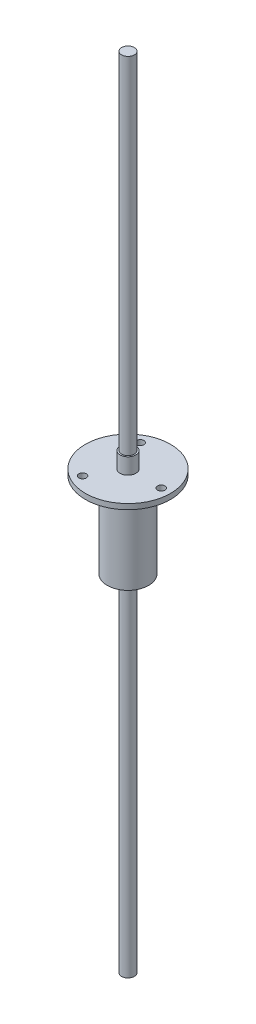
SolidWorks part; units mm, degrees
ref_plane "Front Plane" through (0, 0, 0) normal (0, 0, 1) x (1, 0, 0)
ref_plane "Top Plane" through (0, 0, 0) normal (0, 1, 0) x (1, 0, 0)
ref_plane "Right Plane" through (0, 0, 0) normal (1, 0, 0) x (0, 0, -1)
sketch "Sketch1" plane through (0, 0, 0) normal (1, 0, 0) x (0, 0, -1)
  line L0 (0, 23.9311) -> (0, -15.9842) construction
  line L1 (0, 20.05) -> (2.95, 20.05)
  line L2 (2.95, 20.05) -> (2.95, 14.05)
  line L3 (2.95, 14.05) -> (16, 14.05)
  line L4 (16, 14.05) -> (16, 12.05)
  line L5 (16, 12.05) -> (7.75, 12.05)
  line L6 (7.75, 12.05) -> (7.75, -20.05)
  line L7 (7.75, -20.05) -> (0, -20.05)
  line L8 (0, -20.05) -> (0, 20.05)
  point P11 (0, 23.0883)
  point P12 (7.75, -19.6566)
  dimension "D1" = 5.9
  dimension "D2" = 34.1
  dimension "D3" = 2
  dimension "D4" = 6
  dimension "D5" = 32
  dimension "D6" = 15.5
revolve "Revolve1" add sketch "Sketch1" angle 360 about L0
sketch "Sketch2" plane through (0, 14.05, 0) normal (0, 1, 0) x (1, 0, 0)
  circle A0 centre (0, 0) radius 12.5 construction
  circle A1 centre (12.5, 0) radius 1.4
  circle A2 centre (-6.25, -10.8253) radius 1.4
  circle A3 centre (-6.25, 10.8253) radius 1.4
  point P6 (0, 0)
  point P7 (0, 0)
  point P11 (0, 0)
  dimension "D1" = 3
  dimension "D2" = 25
  dimension "D3" = 2.8
extrude "Cut-Extrude1" cut sketch "Sketch2" against normal through all both
sketch "Sketch3" plane through (0, 0, 0) normal (0, 1, 0) x (1, 0, 0)
  circle A0 centre (0, 0) radius 2.4
  dimension "D1" = 4.8
extrude "Boss-Extrude1" add sketch "Sketch3" along normal mid plane 300
